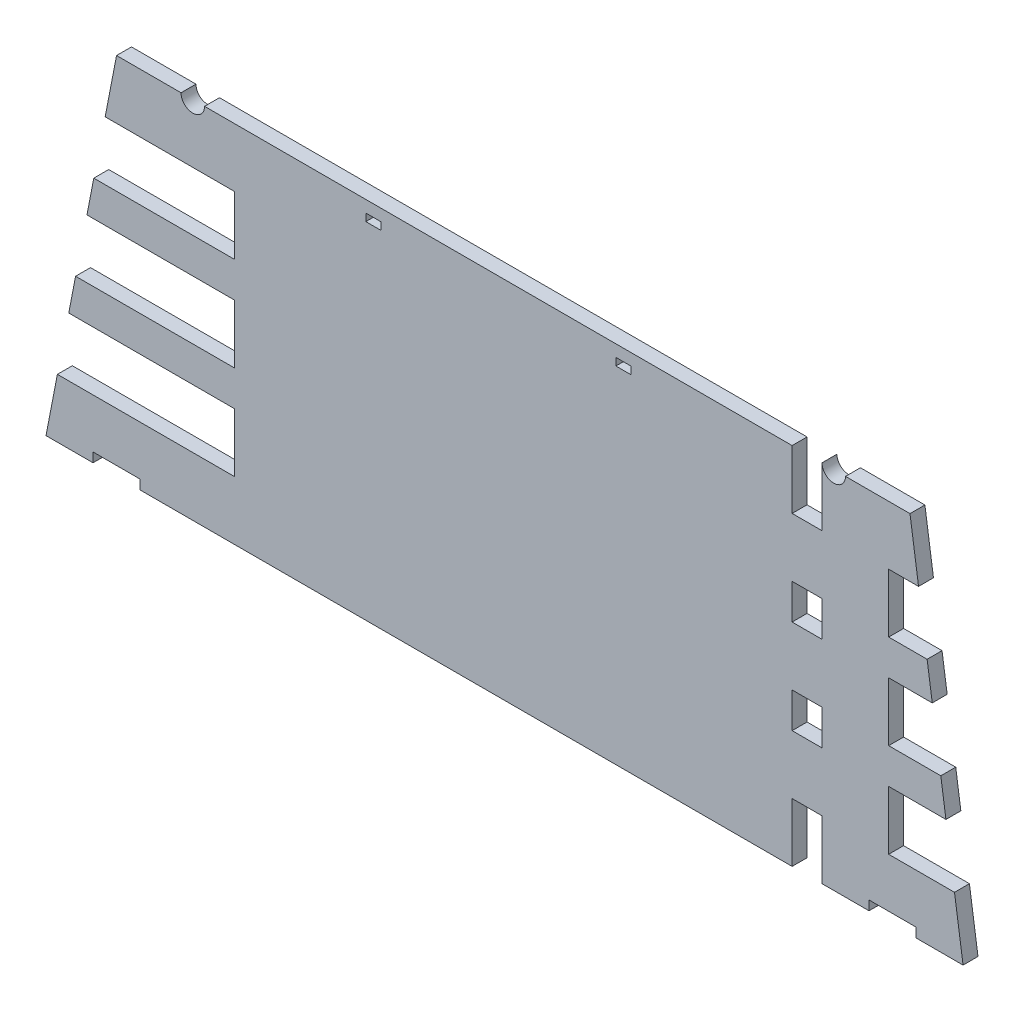
SolidWorks part; units mm, degrees
ref_plane "Front Plane" through (0, 0, 0) normal (0, 0, 1) x (1, 0, 0)
ref_plane "Top Plane" through (0, 0, 0) normal (0, 1, 0) x (1, 0, 0)
ref_plane "Right Plane" through (0, 0, 0) normal (1, 0, 0) x (0, 0, -1)
sketch "Sketch1" plane through (0, 0, 0) normal (0, 0, 1) x (1, 0, 0)
  line L0 (-152.3625, 0) -> (124.9375, 0)
  line L1 (197.6375, 0) -> (193.9964, 25)
  line L2 (175.0625, 155) -> (147.6375, 155)
  line L3 (-162.3625, 155) -> (-167.2012, 130)
  line L4 (-192.3625, 0) -> (-172.3625, 0)
  line L5 (-172.3625, 0) -> (-172.3625, 4)
  line L6 (-172.3625, 4) -> (-152.3625, 4)
  line L7 (-152.3625, 4) -> (-152.3625, 0)
  line L8 (-162.3625, 155) -> (-134.9375, 155)
  line L9 (157.6375, 0) -> (157.6375, 4)
  line L10 (157.6375, 4) -> (177.6375, 4)
  line L11 (177.6375, 4) -> (177.6375, 0)
  line L12 (177.6375, 0) -> (197.6375, 0)
  line L13 (-162.3625, 155) -> (-134.9375, 155)
  line L14 (0, 155) -> (0, 0) construction
  line L15 (-124.9375, 155) -> (124.9375, 155)
  line L16 (-167.2012, 130) -> (-112.2375, 130)
  line L17 (-112.2375, 130) -> (-112.2375, 105)
  line L18 (-112.2375, 105) -> (-172.0399, 105)
  line L19 (-174.9431, 90) -> (-112.2375, 90)
  line L20 (-112.2375, 90) -> (-112.2375, 65)
  line L21 (-112.2375, 65) -> (-179.7819, 65)
  line L22 (-182.6851, 50) -> (-112.2375, 50)
  line L23 (-112.2375, 50) -> (-112.2375, 25)
  line L24 (-112.2375, 25) -> (-187.5238, 25)
  line L25 (-172.0399, 105) -> (-174.9431, 90)
  line L26 (-179.7819, 65) -> (-182.6851, 50)
  line L27 (-187.5238, 25) -> (-192.3625, 0)
  line L28 (124.9375, 90) -> (124.9375, 105)
  line L29 (124.9375, 105) -> (137.6375, 105)
  line L30 (137.6375, 105) -> (137.6375, 90)
  line L31 (137.6375, 90) -> (124.9375, 90)
  line L32 (-112.2375, 105) -> (-112.2375, 90) construction
  line L33 (124.9375, 50) -> (124.9375, 65)
  line L34 (124.9375, 65) -> (137.6375, 65)
  line L35 (137.6375, 65) -> (137.6375, 50)
  line L36 (137.6375, 50) -> (124.9375, 50)
  line L37 (137.6375, 0) -> (137.6375, 25)
  line L38 (137.6375, 25) -> (124.9375, 25)
  line L39 (124.9375, 25) -> (124.9375, 0)
  line L40 (124.9375, 155) -> (124.9375, 130)
  line L41 (124.9375, 130) -> (137.6375, 130)
  line L42 (137.6375, 130) -> (137.6375, 155)
  line L43 (137.6375, 0) -> (157.6375, 0)
  line L44 (178.7036, 130) -> (166.0036, 130)
  line L45 (166.0036, 130) -> (166.0036, 105)
  line L46 (166.0036, 105) -> (182.3448, 105)
  line L47 (184.5294, 90) -> (166.0036, 90)
  line L48 (166.0036, 90) -> (166.0036, 65)
  line L49 (166.0036, 65) -> (188.1706, 65)
  line L50 (190.3552, 50) -> (166.0036, 50)
  line L51 (166.0036, 50) -> (166.0036, 25)
  line L52 (166.0036, 25) -> (193.9964, 25)
  line L53 (190.3552, 50) -> (188.1706, 65)
  line L54 (184.5294, 90) -> (182.3448, 105)
  line L55 (178.7036, 130) -> (175.0625, 155)
  line L56 (-56.35, 150) -> (-56.35, 146.825)
  line L57 (-56.35, 146.825) -> (-50, 146.825)
  line L58 (-50, 146.825) -> (-50, 150)
  line L59 (-50, 150) -> (-56.35, 150)
  line L60 (50, 150) -> (56.35, 150)
  line L61 (50, 146.825) -> (50, 150)
  line L62 (56.35, 146.825) -> (50, 146.825)
  line L63 (56.35, 150) -> (56.35, 146.825)
  arc A0 (-134.9375, 155) -> (-124.9375, 155) centre (-129.9375, 155) ccw
  arc A1 (147.6375, 155) -> (137.6375, 155) centre (142.6375, 155) cw
  dimension "D18" = 6.35
  dimension "D2" = 20
  dimension "D3" = 20
  dimension "D4" = 282.575
  dimension "D5" = 15
  dimension "D6" = 10
  dimension "D7" = 12.7
  dimension "D8" = 4
  dimension "D9" = 10
  dimension "D10" = 310
  dimension "D11" = 5
  dimension "D12" = 25
  dimension "D13" = 12.7
  dimension "D14" = 25
  dimension "D15" = 12.7
  dimension "D16" = 155
  dimension "D17" = 50
  dimension "D19" = 3.175
  dimension "D20" = 5
extrude "Extrude1" add sketch "Sketch1" along normal blind 6.35 contours L0 L15 A0 L8 L3 L4 L5 L6 L7 | L0 L9 L10 L11 L12 L1 L2 A1 L15 region at (11.4157, 75.9899, 0)
